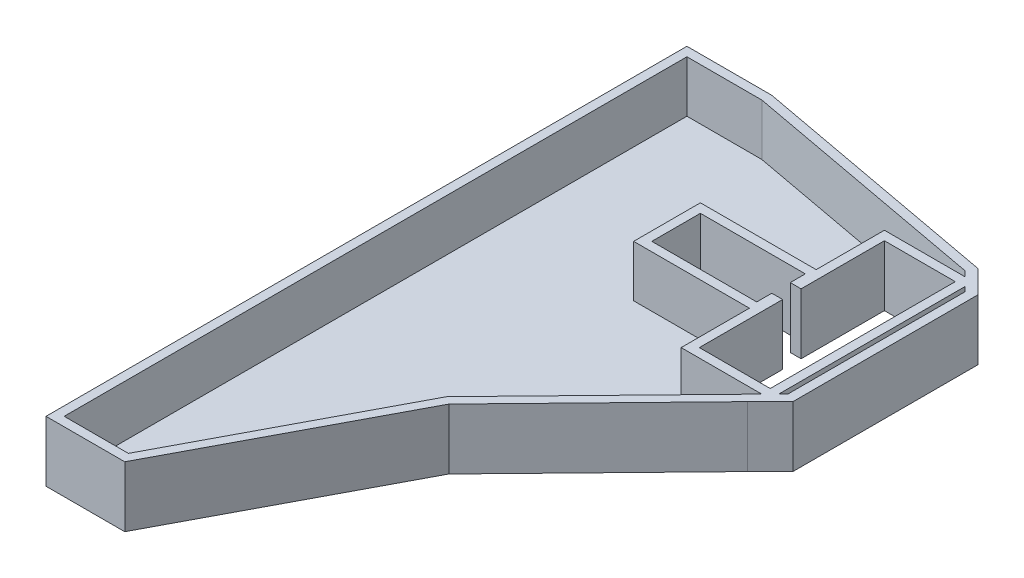
SolidWorks part; units mm, degrees
ref_plane "Front" through (0, 0, 0) normal (0, 0, 1) x (1, 0, 0)
ref_plane "Top" through (0, 0, 0) normal (0, 1, 0) x (1, 0, 0)
ref_plane "Right" through (0, 0, 0) normal (1, 0, 0) x (0, 0, -1)
sketch "Sketch1" plane through (0, 0, 0) normal (0, 1, 0) x (1, 0, 0)
  line L0 (-270.6664, -95.0926) -> (-270.6664, -90.0926) construction
  line L1 (-270.6664, -106.0926) -> (-236.0664, -106.0926) construction
  line L2 (-270.6664, -106.0926) -> (-270.6664, -101.0926) construction
  line L3 (-270.6664, -90.0926) -> (-236.0664, -90.0926) construction
  line L4 (-236.0664, -106.0926) -> (-236.0664, -90.0926) construction
  line L5 (-274.2664, -101.0926) -> (-270.6664, -101.0926) construction
  line L6 (-274.2664, -101.0926) -> (-274.2664, -99.5926) construction
  line L7 (-274.2664, -95.0926) -> (-270.6664, -95.0926) construction
  line L9 (-236.0664, -98.0926) -> (-295.6664, -98.0926) construction
  line L10 (-295.6664, -96.5926) -> (-295.6664, -99.5926) construction
  line L11 (-295.6664, -96.5926) -> (-274.2664, -96.5926) construction
  line L12 (-295.6664, -99.5926) -> (-274.2664, -99.5926) construction
  line L14 (-274.2664, -96.5926) -> (-274.2664, -95.0926) construction
  line L39 (0, 127.7659) -> (0, -127.7659) construction
  line L40 (88.2, 3) -> (84.6, 3) construction
  line L41 (88.2, 1.5) -> (88.2, 3) construction
  line L42 (109.6, 1.5) -> (88.2, 1.5) construction
  line L43 (109.6, 1.5) -> (109.6, -1.5) construction
  line L44 (109.6, -1.5) -> (88.2, -1.5) construction
  line L45 (88.2, -3) -> (88.2, -1.5) construction
  line L46 (88.2, -3) -> (84.6, -3) construction
  line L47 (84.6, -8) -> (84.6, -3) construction
  line L48 (84.6, -8) -> (50, -8) construction
  line L49 (50, -8) -> (50, 8) construction
  line L50 (84.6, 8) -> (50, 8) construction
  line L51 (84.6, 3) -> (84.6, 8) construction
  line L64 (0, 0) -> (50, 0) construction
  line L65 (84.62, 3.05) -> (84.62, 8.02)
  line L66 (84.62, 8.02) -> (49.98, 8.02)
  line L67 (49.98, -8.02) -> (49.98, 8.02)
  line L68 (84.62, -8.02) -> (49.98, -8.02)
  line L69 (84.62, -8.02) -> (84.62, -3.05)
  line L70 (84.62, 3) -> (84.62, 8.02) construction
  line L71 (84.62, -8.02) -> (84.62, -3) construction
  line L72 (84.62, -3.05) -> (88.2, -3.05)
  line L73 (88.2, -3.05) -> (88.2, -30.55)
  line L74 (109.6, 0) -> (111.6, 0) construction
  line L75 (111.6, 30.55) -> (111.6, -30.55)
  line L76 (111.6, -30.55) -> (88.2, -30.55)
  line L77 (84.62, 3.05) -> (88.2, 3.05)
  line L78 (88.2, 3.05) -> (88.2, 30.55)
  line L79 (88.2, 30.55) -> (111.6, 30.55)
  line L80 (111.6, 38.05) -> (28, 53.55)
  line L81 (28, 53.55) -> (0, 53.55)
  line L82 (111.6, 38.05) -> (119.1, 30.55)
  line L83 (119.1, 30.55) -> (119.1, -30.55)
  line L84 (119.1, -30.55) -> (111.6, -38.05)
  line L85 (111.6, 30.55) -> (111.6, 38.05) construction
  line L86 (111.6, 30.55) -> (119.1, 30.55) construction
  line L87 (111.6, 38.05) -> (0, 38.05) construction
  line L88 (111.6, -30.55) -> (119.1, -30.55) construction
  line L89 (111.6, -30.55) -> (111.6, -38.05) construction
  line L90 (111.6, -38.05) -> (63, -88.05)
  line L91 (63, -88.05) -> (26, -158.05)
  line L92 (26, -158.05) -> (0, -158.05)
  line L93 (0, -158.05) -> (0, 53.55)
  line L94 (63, -88.05) -> (0, -88.05) construction
  line L95 (26, -158.05) -> (26, -88.05) construction
  line L96 (111.6, -38.05) -> (0, -38.05) construction
  line L97 (63, -88.05) -> (63, -38.05) construction
  point P13 (-295.6664, -98.0926)
  point P21 (0, 0)
  point P36 (111.6, 0)
  dimension "D1" = 16
  dimension "D2" = 34.6
  dimension "D3" = 6
  dimension "D4" = 3.6
  dimension "D5" = 25
  dimension "D6" = 3
  dimension "D7" = 0.02
  dimension "D8" = 0.05
  dimension "D9" = 0.05
  dimension "D10" = 27.5
  dimension "D11" = 2
  dimension "D12" = 50
  dimension "D13" = 28
  dimension "D14" = 7.5
  dimension "D15" = 63
  dimension "D16" = 70
  dimension "D17" = 50
  dimension "D18" = 26
  dimension "D19" = 15.5
extrude "Boss-Extrude2" add sketch "Sketch1" along normal blind 20
shell "Shell1" thickness 3 removed face at (64.2667, 20, 33.0056)
